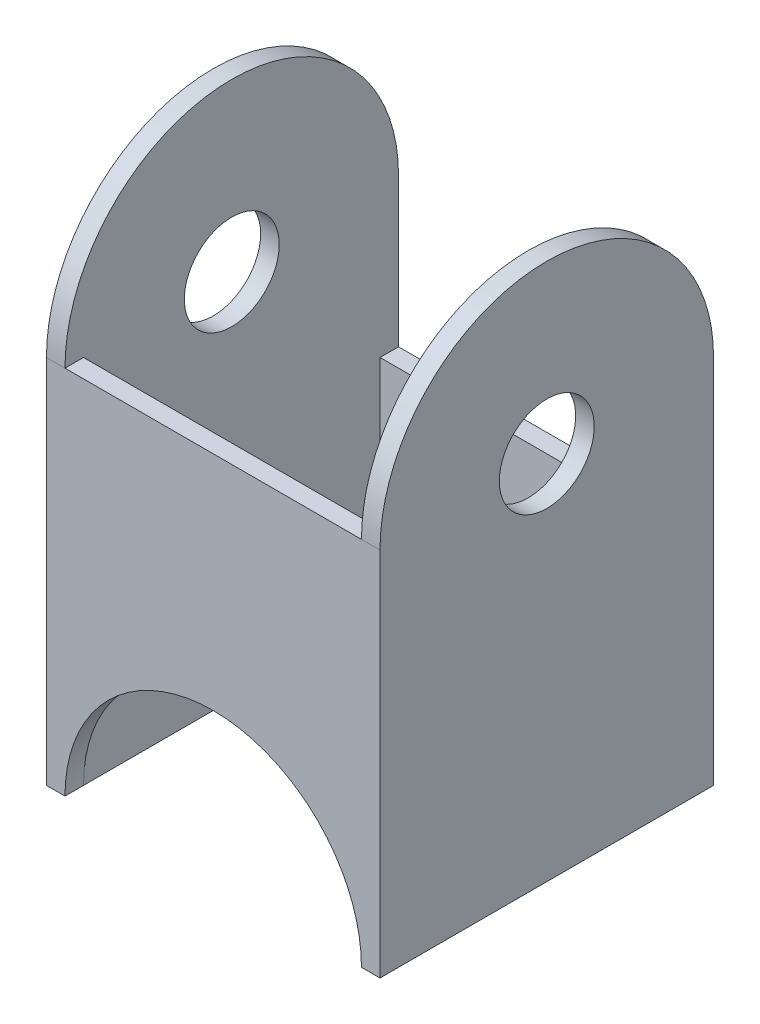
SolidWorks part; units mm, degrees
material "AISI 4130 Steel, annealed at 865C"
ref_plane "Front Plane" through (0, 0, 0) normal (0, 0, 1) x (1, 0, 0)
ref_plane "Top Plane" through (0, 0, 0) normal (0, 1, 0) x (1, 0, 0)
ref_plane "Right Plane" through (0, 0, 0) normal (1, 0, 0) x (0, 0, -1)
sketch "Sketch1" plane through (0, 0, 0) normal (0, 1, 0) x (1, 0, 0)
  line L1 (-12.7, 12.7) -> (12.7, 12.7)
  line L2 (-12.7, 12.7) -> (-12.7, -12.7)
  line L3 (-12.7, -12.7) -> (12.7, -12.7)
  line L4 (12.7, 12.7) -> (12.7, -12.7)
  line L5 (-12.7, 12.7) -> (12.7, -12.7) construction
  line L6 (-12.7, -12.7) -> (12.7, 12.7) construction
  line L7 (-14.2875, 14.2875) -> (14.2875, 14.2875)
  line L8 (-14.2875, 14.2875) -> (-14.2875, -14.2875)
  line L9 (-14.2875, -14.2875) -> (14.2875, -14.2875)
  line L10 (14.2875, 14.2875) -> (14.2875, -14.2875)
  line L11 (-14.2875, 14.2875) -> (14.2875, -14.2875) construction
  line L12 (-14.2875, -14.2875) -> (14.2875, 14.2875) construction
  point P0 (0, 0)
  point P6 (0, 0)
  dimension "D1" = 25.4
  dimension "D2" = 25.4
  dimension "D3" = 1.5875
extrude "Boss-Extrude1" add sketch "Sketch1" along normal blind 31.75
sketch "Sketch2" plane through (-14.2875, 0, 0) normal (-1, 0, 0) x (0, 0, 1)
  line L0 (-14.2875, 31.75) -> (14.2875, 31.75) construction
  circle A0 centre (0, 31.75) radius 14.2875
extrude "Boss-Extrude2" add sketch "Sketch2" against normal up to surface (1.5875 mm away) up to face at (-12.7, 15.875, 0)
sketch "Sketch3" plane through (14.2875, 0, 0) normal (1, 0, 0) x (0, 0, -1)
  line L0 (-14.2875, 31.75) -> (14.2875, 31.75) construction
  circle A0 centre (0, 31.75) radius 14.2875
  arc A1 (14.2875, 31.75) -> (-14.2875, 31.75) centre (0, 31.75) ccw construction
extrude "Boss-Extrude3" add sketch "Sketch3" against normal up to surface (1.5875 mm away) up to face at (12.7, 15.875, 0)
sketch "Sketch4" plane through (-14.2875, 0, 0) normal (-1, 0, 0) x (0, 0, 1)
  circle A0 centre (0, 31.75) radius 4.064
  arc A1 (14.2875, 31.75) -> (-14.2875, 31.75) centre (0, 31.75) ccw construction
  dimension "D1" = 8.128
extrude "Cut-Extrude1" cut sketch "Sketch4" against normal through all both and the other way through all
sketch "Sketch5" plane through (0, 0, 14.2875) normal (0, 0, 1) x (1, 0, 0)
  circle A0 centre (0, 0) radius 12.7
  point P3 (0, 12.7)
  dimension "D1" = 25.4
extrude "Cut-Extrude2" cut sketch "Sketch5" against normal through all both and the other way through all
sketch "Sketch6" plane through (0, 0, -12.7) normal (0, 0, 1) x (1, 0, 0)
  line L0 (12.7, 35.814) -> (12.7, 27.686) construction
  line L1 (-12.7, 31.75) -> (12.7, 31.75)
  line L2 (-12.7, 31.75) -> (-12.7, 19.05)
  line L3 (-12.7, 19.05) -> (12.7, 19.05)
  line L4 (12.7, 31.75) -> (12.7, 19.05)
  line L5 (-12.7, 31.75) -> (12.7, 19.05) construction
  line L6 (-12.7, 19.05) -> (12.7, 31.75) construction
  point P4 (0, 25.4)
  dimension "D1" = 12.7
extrude "Cut-Extrude3" cut sketch "Sketch6" against normal up to next
ref_axis "Axis1" through (14.2875, 31.75, 0) along (-1, 0, 0)
ref_point "Point2"
ref_point "Point4"
